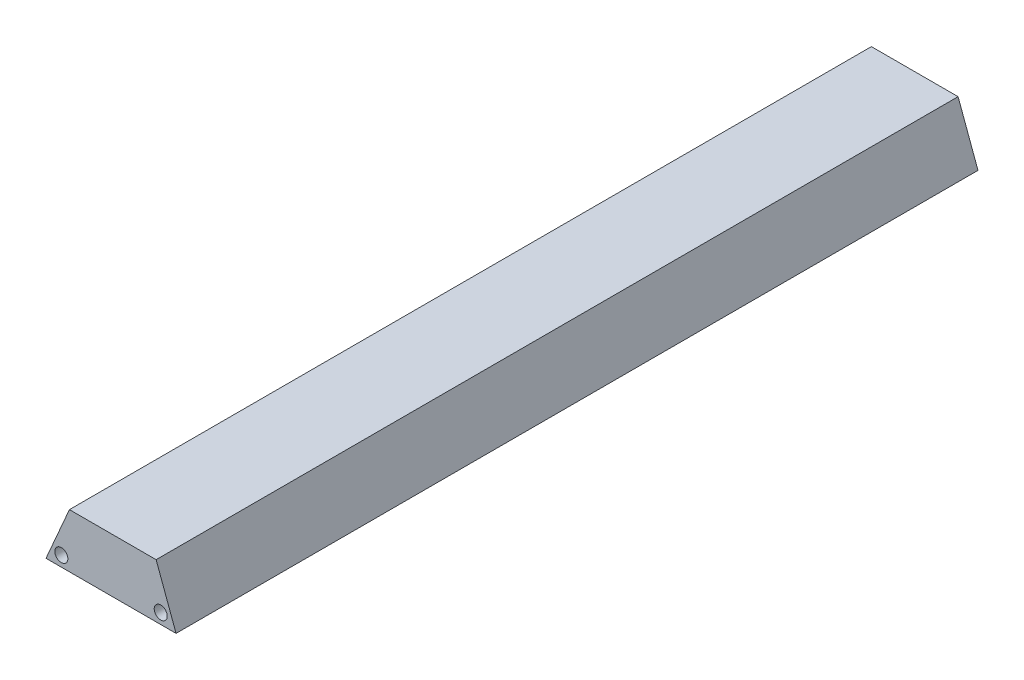
SolidWorks part; units mm, degrees
ref_plane "Front" through (0, 0, 0) normal (0, 0, 1) x (1, 0, 0)
ref_plane "Top" through (0, 0, 0) normal (0, 1, 0) x (1, 0, 0)
ref_plane "Right" through (0, 0, 0) normal (1, 0, 0) x (0, 0, -1)
sketch "Sketch1" plane through (0, 0, 0) normal (0, 0, 1) x (1, 0, 0)
  line L0 (-33.496, 0) -> (42.6046, 0) construction
  line L1 (-0.0368, 20.7146) -> (-0.0368, -18.6579) construction
  line L2 (-1.9557, 1.1917) -> (2.0443, 1.1917)
  line L3 (2.0443, 1.1917) -> (2.9632, -1.2948)
  line L4 (2.9632, -1.2948) -> (-3.0368, -1.2948)
  line L5 (-3.0368, -1.2948) -> (-1.9557, 1.1917)
  circle A0 centre (2.2562, -0.813) radius 0.3
  circle A1 centre (-2.3297, -0.813) radius 0.3
  dimension "D1" = 4
  dimension "D2" = 3
  dimension "D3" = 6
extrude "Boss-Extrude1" add sketch "Sketch1" along normal blind 18.5 and the other way blind 18.5
sketch "Sketch3" plane through (0, -1.2948, 0) normal (0, -1, 0) x (-1, 0, 0)
  line L0 (3.0368, 18.5) -> (3.0368, -18.5) construction
  line L1 (-2.9632, 18.5) -> (-2.9632, -18.5) construction
  point P0 (3.0368, 0)
  point P1 (-2.9632, 0)
